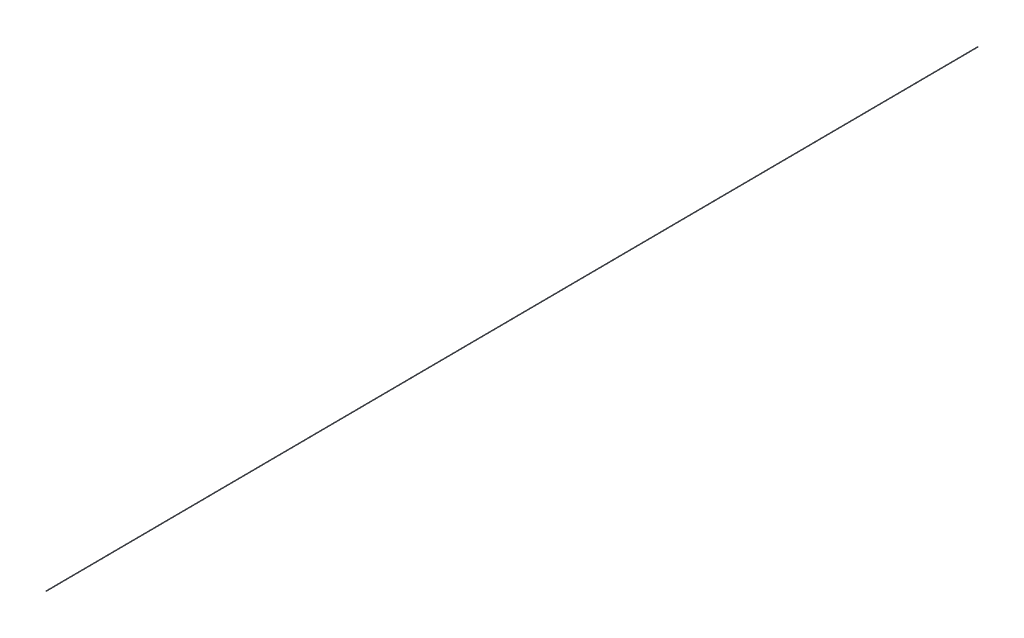
SolidWorks part; units mm, degrees
ref_plane "Front Plane" through (0, 0, 0) normal (0, 0, 1) x (1, 0, 0)
ref_plane "Top Plane" through (0, 0, 0) normal (0, 1, 0) x (1, 0, 0)
ref_plane "Right Plane" through (0, 0, 0) normal (1, 0, 0) x (0, 0, -1)
sketch "Sketch1" plane through (0, 0, 0) normal (1, 0, 0) x (0, 0, -1)
  line L0 (0, 0) -> (14539.79, 0) construction
  line L1 (14539.79, 0) -> (14539.79, 85.55) construction
  line L3 (14539.79, 85.55) -> (14529.79, 85.55)
  line L4 (0, 0) -> (10, 0)
  line L5 (10, 0) -> (14529.79, 85.55)
  point P3 (11.0278, 0)
  dimension "D1" = 14539.79
  dimension "D2" = 10
  dimension "D3" = 10
  dimension "D4" = 85.55
sketch "Sketch2" plane through (0, 0, 0) normal (0, 0, 1) x (1, 0, 0)
  circle A0 centre (0, 0) radius 3.8
  dimension "D1" = 7.6
sweep "Sweep1" add profiles "Sketch2" path "Sketch1"
